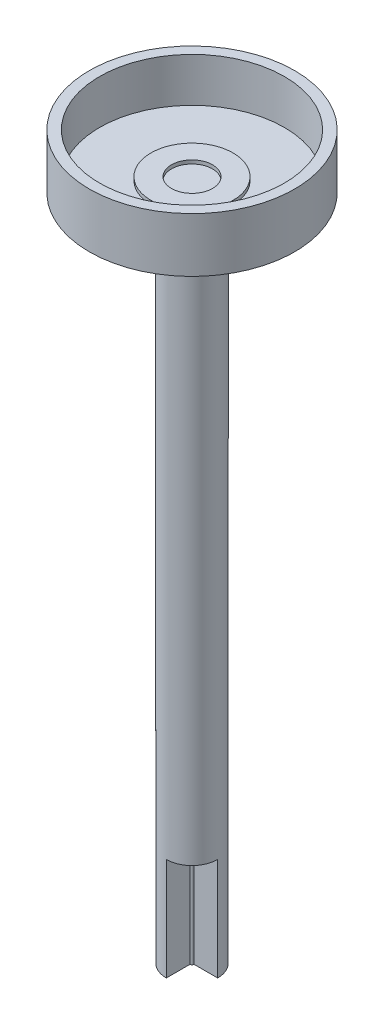
SolidWorks part; units mm, degrees
ref_plane "Front Plane" through (0, 0, 0) normal (0, 0, 1) x (1, 0, 0)
ref_plane "Top Plane" through (0, 0, 0) normal (0, 1, 0) x (1, 0, 0)
ref_plane "Right Plane" through (0, 0, 0) normal (1, 0, 0) x (0, 0, -1)
sketch "Sketch1" plane through (0, 0, 0) normal (0, 1, 0) x (1, 0, 0)
  circle A0 centre (0, 0) radius 10
  circle A1 centre (0, 0) radius 9
  dimension "D1" = 20
  dimension "D2" = 18
extrude "Boss-Extrude1" add sketch "Sketch1" along normal blind 4.3
extrude "Boss-Extrude2" add sketch "Sketch1<2>" against normal blind 1 contours A0
sketch "Sketch1<2>" plane through (0, 0, 0) normal (0, 1, 0) x (1, 0, 0) same geometry as "Sketch1"
sketch "Sketch2" plane through (0, 0, 0) normal (0, 1, 0) x (1, 0, 0)
  circle A0 centre (0, 0) radius 2
  dimension "D1" = 4
extrude "Extrude-Thin1" add sketch "Sketch2" along normal blind 0.35 thin thin type one direction wall 2
sketch "Sketch3" plane through (0, -1, 0) normal (0, -1, 0) x (1, 0, 0)
  circle A0 centre (0, 0) radius 2.5
  dimension "D1" = 5
extrude "Boss-Extrude3" add sketch "Sketch3" along normal blind 65
sketch "Sketch4" plane through (0, -66, 0) normal (0, -1, 0) x (1, 0, 0)
  line L0 (-2.5, 0) -> (-0.195, 0)
  line L1 (0, 2.5) -> (0, 0.195)
  line L2 (0.195, 0) -> (2.5, 0)
  line L3 (0, -0.195) -> (0, -2.5)
  circle A0 centre (0, 0) radius 2.5 construction
  arc A1 (-2.5, 0) -> (0, -2.5) centre (0, 0) ccw
  arc A2 (2.5, 0) -> (0, 2.5) centre (0, 0) ccw
  arc A3 (-0.195, 0) -> (0, -0.195) centre (0, 0) ccw
  arc A4 (0.195, 0) -> (0, 0.195) centre (0, 0) ccw
  point P5 (0, 0)
  point P9 (0, 0)
extrude "Cut-Extrude1" cut sketch "Sketch4" against normal blind 10
